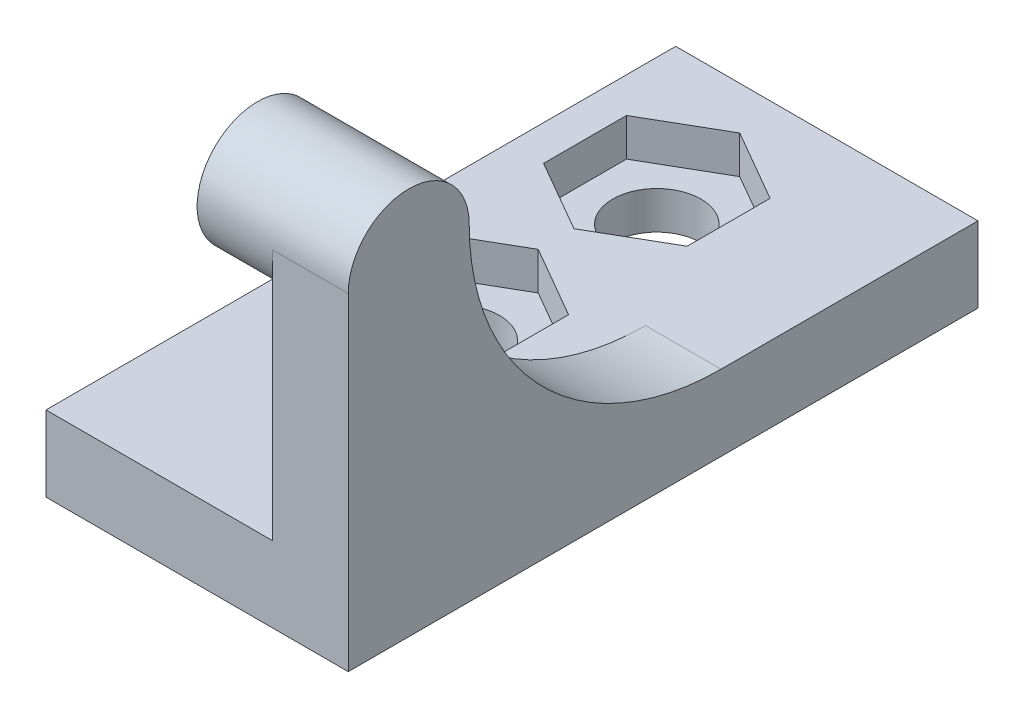
SolidWorks part; units mm, degrees
ref_plane "Plan de face" through (0, 0, 0) normal (0, 0, 1) x (1, 0, 0)
ref_plane "Plan de dessus" through (0, 0, 0) normal (0, 1, 0) x (1, 0, 0)
ref_plane "Plan de droite" through (0, 0, 0) normal (1, 0, 0) x (0, 0, -1)
sketch "Esquisse1" plane through (0, 0, 0) normal (1, 0, 0) x (0, 0, -1)
  circle A0 centre (0, 0) radius 2.4
  dimension "D1" = 4.8
extrude "Boss.-Extru.1" add sketch "Esquisse1" along normal blind 3
sketch "Esquisse2" plane through (3, 0, 0) normal (1, 0, 0) x (0, 0, -1)
  line L1 (-2.4, 0) -> (2.4, 0) construction
  line L2 (-2.4, 0) -> (-2.4, -10)
  line L3 (-2.4, -10) -> (2.4, -10)
  line L4 (2.4, 0) -> (2.4, -10)
  circle A0 centre (0, 0) radius 2.4 construction
  arc A1 (-2.4, 0) -> (2.4, 0) centre (0, 0) cw
  dimension "D1" = 10
extrude "Boss.-Extru.2" add sketch "Esquisse2" along normal blind 3
sketch "Esquisse3" plane through (0, -10, 0) normal (0, -1, 0) x (1, 0, 0)
  line L0 (3, 2.4) -> (3, -2.4) construction
  line L1 (6, 2.4) -> (-6, 2.4)
  line L2 (6, 2.4) -> (6, -22.6)
  line L3 (6, -22.6) -> (-6, -22.6)
  line L4 (-6, 2.4) -> (-6, -22.6)
  line L5 (-1.75, -9.6) -> (-1.75, -17.6) construction
  circle A0 centre (-1.75, -9.6) radius 1.75
  circle A1 centre (-1.75, -17.6) radius 1.75
  dimension "D2" = 3.5
  dimension "D1" = 12
  dimension "D3" = 4.75
  dimension "D4" = 12
  dimension "D5" = 25
  dimension "D6" = 8
extrude "Boss.-Extru.3" add sketch "Esquisse3" along normal blind 3
sketch "Esquisse4" plane through (0, -10, 0) normal (0, 1, 0) x (1, 0, 0)
  line L0 (-4.6, 7.9546) -> (-4.6, 11.2454)
  line L1 (-4.6, 11.2454) -> (-1.75, 12.8909)
  line L2 (-1.75, 12.8909) -> (1.1, 11.2454)
  line L3 (1.1, 11.2454) -> (1.1, 7.9546)
  line L4 (1.1, 7.9546) -> (-1.75, 6.3091)
  line L5 (-1.75, 6.3091) -> (-4.6, 7.9546)
  line L6 (-4.6, 11.2454) -> (1.1, 7.9546) construction
  line L7 (-1.75, 12.8909) -> (-1.75, 6.3091) construction
  line L8 (-4.6, 15.9546) -> (-4.6, 19.2454)
  line L9 (-4.6, 19.2454) -> (-1.75, 20.8909)
  line L10 (-1.75, 20.8909) -> (1.1, 19.2454)
  line L11 (1.1, 19.2454) -> (1.1, 15.9546)
  line L12 (1.1, 15.9546) -> (-1.75, 14.3091)
  line L13 (-1.75, 14.3091) -> (-4.6, 15.9546)
  line L14 (-4.6, 19.2454) -> (1.1, 15.9546) construction
  line L15 (-1.75, 20.8909) -> (-1.75, 14.3091) construction
  point P6 (-1.75, 9.6)
  point P7 (-1.75, 17.6)
  point P8 (-1.75, 9.6)
  point P17 (-1.75, 17.6)
  point P18 (-1.75, 17.6)
  dimension "D1" = 120
  dimension "D2" = 5.7
  dimension "D3" = 120
  dimension "D4" = 5.7
extrude "Enlèv. mat.-Extru.1" cut sketch "Esquisse4" against normal blind 1.5
fillet "Congé1" radius 10 1 edges at (4.5, -10, -2.4)
